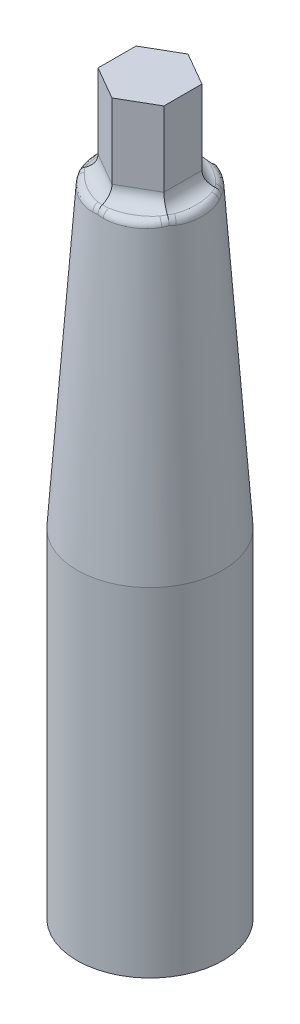
SolidWorks part; units mm, degrees
ref_plane "Front Plane" through (0, 0, 0) normal (0, 0, 1) x (1, 0, 0)
ref_plane "Top Plane" through (0, 0, 0) normal (0, 1, 0) x (1, 0, 0)
ref_plane "Right Plane" through (0, 0, 0) normal (1, 0, 0) x (0, 0, -1)
sketch "Sketch1" plane through (0, 0, 0) normal (0, 1, 0) x (1, 0, 0)
  circle A0 centre (0, 0) radius 2.05
  dimension "D1" = 4.1
extrude "Boss-Extrude1" add sketch "Sketch1" along normal blind 18
chamfer "Chamfer1" distance 8.5 angle 4 1 edges at (0, 18, 2.05) first distance on face at (0, 18, 2.05)
sketch "Sketch3" plane through (0, 18, 0) normal (0, 1, 0) x (1, 0, 0)
  line L1 (0, 1.0681) -> (-0.925, 0.534)
  line L2 (-0.925, 0.534) -> (-0.925, -0.534)
  line L3 (-0.925, -0.534) -> (0, -1.0681)
  line L4 (0, -1.0681) -> (0.925, -0.534)
  line L5 (0.925, -0.534) -> (0.925, 0.534)
  line L6 (0.925, 0.534) -> (0, 1.0681)
  circle A0 centre (0, 0) radius 0.925 construction
  dimension "D1" = 1.85
extrude "Boss-Extrude2" add sketch "Sketch3" along normal blind 2.5 and the other way blind 4
fillet "Fillet2" radius 0.4 6 edges at (-0.4625, 18, -0.8011) (-0.925, 18, 0) (-0.4625, 18, 0.8011) (0.4625, 18, 0.8011) (0.925, 18, 0) (0.4625, 18, -0.8011)
fillet "Fillet3" radius 0.2 18 edges at (1.4556, 18, 0) (0.7278, 18, 1.2606) (-0.7278, 18, 1.2606) (0.7278, 18, -1.2606) (-0.7278, 18, -1.2606) (-1.4556, 18, 0)
sketch "Sketch4" plane through (0, 0, 0) normal (0, -1, 0) x (1, 0, 0)
  circle A0 centre (0, 0) radius 1.3
  circle A1 centre (0, 0) radius 2.05 construction
  dimension "D1" = 0.75
extrude "Cut-Extrude1" cut sketch "Sketch4" against normal blind 10
chamfer "Chamfer2" distance 1.85 angle 35 1 edges at (0, 10, -1.3) first distance on face at (0, 10, -1.3)
sketch "Sketch6" plane through (0, 20.5, 0) normal (0, 1, 0) x (1, 0, 0)
  line L0 (0, 0) -> (0, 2.05) construction
  line L2 (-0.4, 2.5402) -> (0.4, 2.5402)
  line L3 (-0.4, 2.5402) -> (-0.4, 1.25)
  line L4 (-0.4, 1.25) -> (0.4, 1.25)
  line L5 (0.4, 2.5402) -> (0.4, 1.25)
  circle A0 centre (0, 0) radius 2.05 construction
  dimension "D1" = 0.4
  dimension "D2" = 0.4
  dimension "D3" = 1.25
extrude "Cut-Extrude2" cut sketch "Sketch6" against normal blind 10.9 and the other way through all
fillet "Fillet4" radius 0.1 8 edges at (0.4, 17.9391, -1.3614) (-0.4, 17.9302, -1.3691) (-0.4, 9.6, -1.6267) (0.4, 9.6, -1.6267) (0, 9.6, -1.25) (0, 9.6, -2.043)
sketch "Sketch7" plane through (0, 0, -1.25) normal (0, 0, -1) x (-1, 0, 0)
  line L0 (-0.4, 17.8673) -> (-0.4, 9.7) construction
  line L1 (-0.4, 14.25) -> (0.4, 14.25)
  line L2 (-0.4, 14.25) -> (-0.4, 12.75)
  line L3 (-0.4, 12.75) -> (0.4, 12.75)
  line L4 (0.4, 14.25) -> (0.4, 12.75)
  line L5 (0.4, 17.8111) -> (0.4, 9.7) construction
  line L6 (-2.05, 0) -> (2.05, 0) construction
  dimension "D1" = 12.75
  dimension "D2" = 1.5
extrude "Cut-Extrude3" cut sketch "Sketch7" against normal blind 0.5
chamfer "Chamfer3" distance 0.87 angle 30 1 edges at (0, 14.25, -0.75) first distance on face at (0, 13.5, -0.75)
